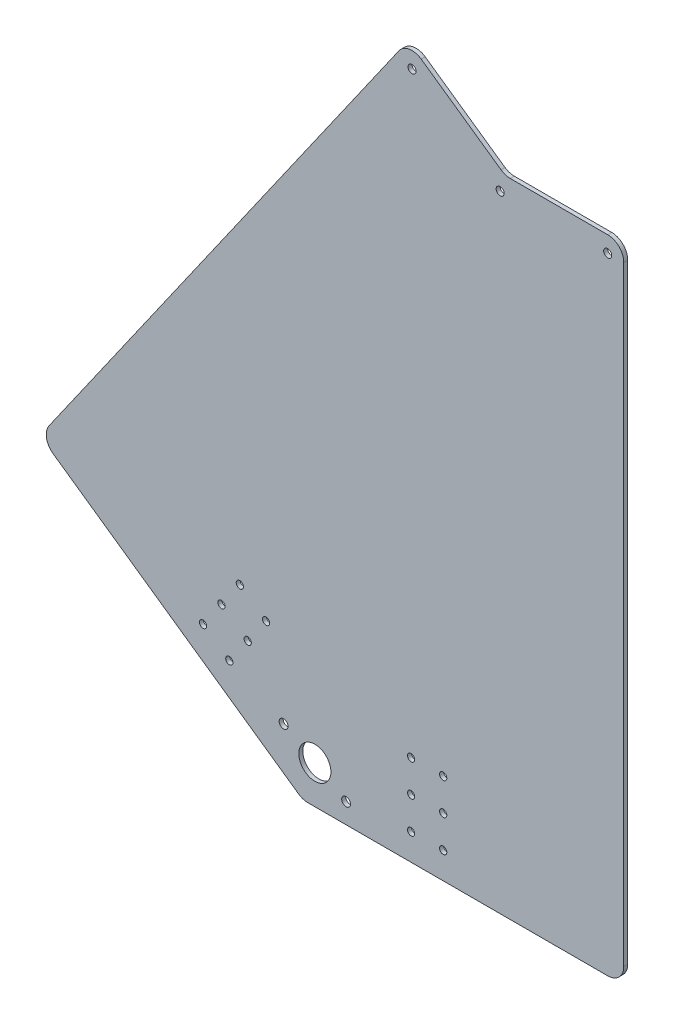
SolidWorks part; units mm, degrees
ref_plane "Front Plane" through (0, 0, 0) normal (0, 0, 1) x (1, 0, 0)
ref_plane "Top Plane" through (0, 0, 0) normal (0, 1, 0) x (1, 0, 0)
ref_plane "Right Plane" through (0, 0, 0) normal (1, 0, 0) x (0, 0, -1)
sketch "Sketch1" plane through (0, 0, 0) normal (0, 0, 1) x (1, 0, 0)
  line L0 (0, 0) -> (400, 0)
  line L1 (400, 0) -> (400, 800)
  line L2 (400, 800) -> (252.239, 800)
  line L3 (252.239, 800) -> (131.2003, 884.7522)
  line L4 (131.2003, 884.7522) -> (-327.6608, 229.4306)
  line L5 (-327.6608, 229.4306) -> (0, 0)
  dimension "D1" = 145
  dimension "D2" = 800
  dimension "D3" = 400
base flange "Base-Flange1" sketch "Sketch1" thickness 5 reverse thickness direction no parameters "D1"=1
fillet "Fillet1" radius 20 6 edges at (400, 0, -2.5) (0, 0, -2.5) (-327.6608, 229.4306, -2.5) (252.239, 800, -2.5) (400, 800, -2.5) (131.2003, 884.7522, -2.5)
hole_wizard "Ø10.0 (10) Diameter Hole1" positions "Sketch6" profile "Sketch7" hole size "Ø10.0" standard "ISO" end condition through all
sketch "Sketch6" plane through (0, 0, 0) normal (0, 0, 1) x (1, 0, 0)
  line L0 (252.239, 800) -> (0, 0) construction
  line L2 (380, 800) -> (258.545, 800) construction
  point P0 (245.9331, 780)
  point P15 (136.1118, 856.8976)
  point P18 (380, 780)
  dimension "D1" = 20
sketch "Sketch7" plane through (245.9331, 780, 0) normal (1, 0, 0) x (0, -1, 0)
  line L0 (0, 0) -> (0, 5)
  line L1 (0, 5) -> (5, 5)
  line L2 (5, 5) -> (5, 0)
  line L5 (5, 0) -> (0, 0)
  line L11 (0, -6.35) -> (0, 107.95) construction
  dimension "Thru Hole Dia." = 10
  dimension "Thru Hole Depth" = 5
sketch "Sketch10" plane through (0, 0, 0) normal (0, 0, 1) x (1, 0, 0)
  line L0 (6.306, 0) -> (380, 0) construction
  line L1 (252.239, 800) -> (0, 0) construction
  circle A0 centre (14.9767, 47.5) radius 20
  dimension "D1" = 40
  dimension "D2" = 47.5
extrude "Cut-Extrude1" cut sketch "Sketch10" against normal through all normal cut yes
hole_wizard "M10 Clearance Hole3" positions "Sketch11" profile "Sketch12" hole size "M10" standard "ISO" end condition through all
sketch "Sketch11" plane through (0, 0, 0) normal (0, 0, 1) x (1, 0, 0)
  line L0 (-23.9945, 70) -> (53.9478, 25) construction
  line L2 (6.306, 0) -> (380, 0) construction
  circle A0 centre (14.9767, 47.5) radius 20 construction
  point P0 (-23.9945, 70)
  point P2 (53.9478, 25)
  point P9 (14.9767, 47.5)
  dimension "D1" = 90
  dimension "D2" = 30
sketch "Sketch12" plane through (-23.9945, 70, 0) normal (1, 0, 0) x (0, -1, 0)
  line L0 (0, 0) -> (0, 5)
  line L1 (0, 5) -> (5.5, 5)
  line L2 (5.5, 5) -> (5.5, 0)
  line L5 (5.5, 0) -> (0, 0)
  line L11 (0, -6.35) -> (0, 107.95) construction
  dimension "Thru Hole Dia." = 11
  dimension "Thru Hole Depth" = 5
hole_wizard "M8 Clearance Hole1" positions "Sketch13" profile "Sketch14" hole size "M8" standard "ISO" end condition through all
sketch "Sketch13" plane through (0, 0, 0) normal (0, 0, 1) x (1, 0, 0)
  line L0 (-124.4045, 127.3945) -> (-78.5184, 192.9267) construction
  line L1 (-124.4045, 127.3945) -> (-91.6384, 104.4515) construction
  line L2 (-78.5184, 192.9267) -> (-45.7523, 169.9836) construction
  line L3 (-91.6384, 104.4515) -> (-45.7523, 169.9836) construction
  line L4 (119.7288, 868.3692) -> (-316.1893, 245.8136) construction
  line L7 (134.9767, 113) -> (174.9767, 113) construction
  line L8 (134.9767, 113) -> (134.9767, 33) construction
  line L9 (134.9767, 33) -> (174.9767, 33) construction
  line L10 (174.9767, 113) -> (174.9767, 33) construction
  line L13 (252.239, 800) -> (0, 0) construction
  line L15 (-45.7523, 169.9836) -> (35.6288, 113) construction
  line L17 (134.9767, 113) -> (35.6288, 113) construction
  circle A0 centre (14.9767, 47.5) radius 20 construction
  point P2 (-124.4045, 127.3945)
  point P3 (-78.5184, 192.9267)
  point P75 (-45.7523, 169.9836)
  point P76 (-91.6384, 104.4515)
  point P86 (-101.4614, 160.1606)
  point P91 (-68.6954, 137.2175)
  point P97 (134.9767, 113)
  point P98 (174.9767, 33)
  point P163 (134.9767, 33)
  point P164 (174.9767, 113)
  point P175 (134.9767, 73)
  point P182 (174.9767, 73)
  dimension "D4" = 120
  dimension "D3" = 14.5
  dimension "D1" = 40
  dimension "D2" = 80
sketch "Sketch14" plane through (-124.4045, 127.3945, 0) normal (1, 0, 0) x (0, -1, 0)
  line L0 (0, 0) -> (0, 5)
  line L1 (0, 5) -> (4.5, 5)
  line L2 (4.5, 5) -> (4.5, 0)
  line L5 (4.5, 0) -> (0, 0)
  line L11 (0, -6.35) -> (0, 107.95) construction
  dimension "Thru Hole Dia." = 9
  dimension "Thru Hole Depth" = 5
sketch "Bend-Lines1" [suppressed] plane through (0, 0, 0) normal (0, 1, 0) x (1, 0, 0)
sketch "Bounding-Box1" [suppressed] plane through (0, 0, 0) normal (0, 1, 0) x (1, 0, 0)
sheet metal parameters "Sheet-Metal1" thickness 5 parameters "D1"=1
flat pattern "Flat-Pattern1" [suppressed]
sketch "Bend-Lines2" plane through (0, 0, 0) normal (0, 1, 0) x (1, 0, 0)
sketch3d "Bounding-Box2" [suppressed]
  line L0 (109.8807, 0, 0) -> (-260, 0, 0) construction
  line L1 (109.8807, 318.4732, 0) -> (-260, 318.4732, 0) construction
  line L2 (109.8807, 0, 0) -> (109.8807, 318.4732, 0) construction
  line L3 (-260, 0, 0) -> (-260, 318.4732, 0) construction
sheet metal parameters "Sheet-Metal2" thickness 5 parameters "D1"=1
flat pattern "Flat-Pattern1"
sketch "Bend-Lines2" plane through (0, 0, 0) normal (0, 1, 0) x (1, 0, 0)
sketch3d "Bounding-Box2" [suppressed]
  line L0 (148.7973, 312.1285, 0) -> (278.2865, 34.4381, 0) construction
  line L1 (-92.976, 199.3877, 0) -> (36.5132, -78.3027, 0) construction
  line L2 (148.7973, 312.1285, 0) -> (-92.976, 199.3877, 0) construction
  line L3 (278.2865, 34.4381, 0) -> (36.5132, -78.3027, 0) construction
sheet metal parameters "Sheet-Metal4" thickness 5 parameters "D1"=1
flat pattern "Flat-Pattern1"
sketch "Bend-Lines2" plane through (0, 0, 0) normal (0, 1, 0) x (1, 0, 0)
sketch3d "Bounding-Box2" [suppressed]
  line L0 (148.7973, 312.1285, 0) -> (278.2865, 34.4381, 0) construction
  line L1 (-92.976, 199.3877, 0) -> (36.5132, -78.3027, 0) construction
  line L2 (148.7973, 312.1285, 0) -> (-92.976, 199.3877, 0) construction
  line L3 (278.2865, 34.4381, 0) -> (36.5132, -78.3027, 0) construction
sheet metal parameters "Sheet-Metal5" thickness 5 parameters "D1"=1
flat pattern "Flat-Pattern1"
sketch "Bend-Lines2" plane through (0, 0, 0) normal (0, 1, 0) x (1, 0, 0)
sketch3d "Bounding-Box2" [suppressed]
  line L0 (148.7973, 312.1285, 0) -> (278.2865, 34.4381, 0) construction
  line L1 (-92.976, 199.3877, 0) -> (36.5132, -78.3027, 0) construction
  line L2 (148.7973, 312.1285, 0) -> (-92.976, 199.3877, 0) construction
  line L3 (278.2865, 34.4381, 0) -> (36.5132, -78.3027, 0) construction
sheet metal parameters "Sheet-Metal6" thickness 5 parameters "D1"=1
flat pattern "Flat-Pattern1"
sketch "Bend-Lines2" plane through (0, 0, 0) normal (0, 1, 0) x (1, 0, 0)
sketch3d "Bounding-Box2" [suppressed]
  line L0 (400, 0, 0) -> (400, 876.8976, 0) construction
  line L1 (-319.8062, 0, 0) -> (-319.8062, 876.8976, 0) construction
  line L2 (400, 0, 0) -> (-319.8062, 0, 0) construction
  line L3 (400, 876.8976, 0) -> (-319.8062, 876.8976, 0) construction
